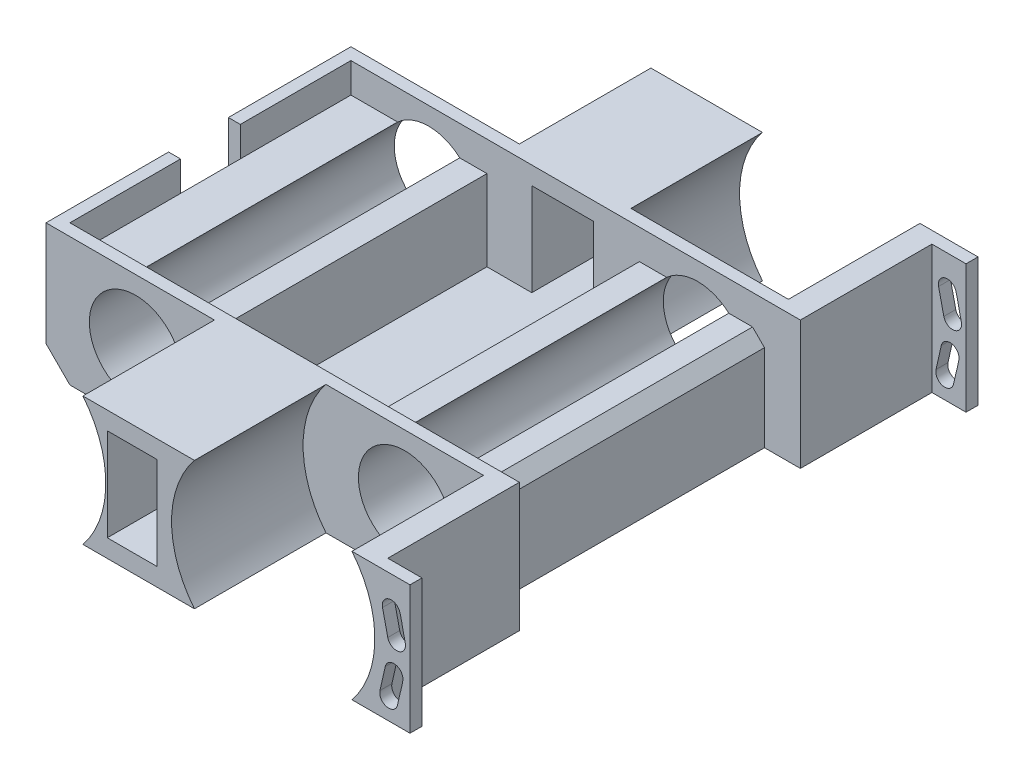
SolidWorks part; units mm, degrees
ref_plane "Front Plane" through (0, 0, 0) normal (0, 0, 1) x (1, 0, 0)
ref_plane "Top Plane" through (0, 0, 0) normal (0, 1, 0) x (1, 0, 0)
ref_plane "Right Plane" through (0, 0, 0) normal (1, 0, 0) x (0, 0, -1)
sketch "Sketch1" plane through (0, 0, 0) normal (0, 1, 0) x (1, 0, 0)
  line L1 (-44.2281, 29.9937) -> (50.7719, 29.9937)
  line L2 (-44.2281, 29.9937) -> (-44.2281, -65.0063)
  line L3 (-44.2281, -65.0063) -> (50.7719, -65.0063)
  line L4 (50.7719, 29.9937) -> (50.7719, -65.0063)
  dimension "D1" = 95
  dimension "D2" = 95
extrude "Boss-Extrude1" add sketch "Sketch1" along normal blind 25
sketch "Sketch2" plane through (0, 0, 65.0063) normal (0, 0, 1) x (1, 0, 0)
  line L1 (-44.2281, 0) -> (50.7719, 0) construction
  line L2 (-44.2281, 25) -> (-44.2281, 0) construction
  circle A0 centre (-29.2281, 10.75) radius 7.75
  circle A1 centre (15.7719, 10.75) radius 7.75
  point P6 (-44.2281, 12.5)
  dimension "D1" = 45
  dimension "D2" = 10.75
  dimension "D3" = 15
extrude "Cut-Extrude2" cut sketch "Sketch2" against normal blind 100
sketch "Sketch3" plane through (0, 0, 65.0063) normal (0, 0, 1) x (1, 0, 0)
  line L0 (-44.2281, 0) -> (50.7719, 0) construction
  circle A0 centre (-29.2281, 10.75) radius 17
  circle A1 centre (15.7719, 10.75) radius 17
  dimension "D1" = 45
  dimension "D2" = 10.75
extrude "Cut-Extrude3" cut sketch "Sketch3" against normal blind 22
sketch "Sketch4" plane through (0, 0, -29.9937) normal (0, 0, -1) x (-1, 0, 0)
  circle A0 centre (-15.7719, 10.75) radius 17
  circle A1 centre (29.2281, 10.75) radius 17
extrude "Cut-Extrude4" cut sketch "Sketch4" against normal blind 22
sketch "Sketch5" plane through (0, 0, 65.0063) normal (0, 0, 1) x (1, 0, 0)
  line L1 (-44.2281, 25) -> (-37.9811, 25)
  line L2 (-44.2281, 25) -> (-44.2281, 0)
  line L3 (-44.2281, 0) -> (-37.9811, 0)
  line L4 (-37.9811, 25) -> (-37.9811, 0)
extrude "Cut-Extrude5" cut sketch "Sketch5" against normal blind 22
sketch "Sketch6" plane through (0, 0, -29.9937) normal (0, 0, -1) x (-1, 0, 0)
  line L1 (44.2281, 25) -> (37.0493, 25)
  line L2 (44.2281, 25) -> (44.2281, 0)
  line L3 (44.2281, 0) -> (37.0493, 0)
  line L4 (37.0493, 25) -> (37.0493, 0)
extrude "Cut-Extrude6" cut sketch "Sketch6" against normal blind 22
sketch "Sketch8" plane through (0, 0, -29.9937) normal (0, 0, -1) x (-1, 0, 0)
  line L1 (-50.7719, 25) -> (48.732, 25)
  line L2 (-50.7719, 25) -> (-50.7719, 21.5)
  line L3 (-50.7719, 21.5) -> (48.732, 21.5)
  line L4 (48.732, 25) -> (48.732, 21.5)
  dimension "D1" = 3.5
extrude "Cut-Extrude7" cut sketch "Sketch8" against normal blind 100
sketch "Sketch9" plane through (0, 0, 65.0063) normal (0, 0, 1) x (1, 0, 0)
  line L0 (-16.0585, 0) -> (2.6024, 0) construction
  line L1 (-11.9781, 18.5) -> (-3.6781, 18.5)
  line L2 (-11.9781, 18.5) -> (-11.9781, 3)
  line L3 (-11.9781, 3) -> (-3.6781, 3)
  line L4 (-3.6781, 18.5) -> (-3.6781, 3)
  arc A0 (-16.0585, 0) -> (-16.0585, 21.5) centre (-29.2281, 10.75) ccw construction
  circle A1 centre (15.7719, 10.75) radius 7.75 construction
  dimension "D1" = 8.3
  dimension "D2" = 15.5
  dimension "D3" = 3
  dimension "D4" = 17.25
  dimension "D5" = 19.45
extrude "Cut-Extrude11" cut sketch "Sketch9" against normal blind 100
sketch "Sketch13" plane through (-3.6781, 0, 0) normal (-1, 0, 0) x (0, 0, 1)
  line L0 (-29.9937, 3) -> (65.0063, 3) construction
  line L1 (-25.9937, 3) -> (61.0063, 3)
  line L2 (-25.9937, 3) -> (-25.9937, 18.5)
  line L3 (-25.9937, 18.5) -> (61.0063, 18.5)
  line L4 (61.0063, 3) -> (61.0063, 18.5)
  line L5 (-29.9937, 18.5) -> (65.0063, 18.5) construction
  line L6 (-29.9937, 3) -> (-29.9937, 18.5) construction
  line L7 (65.0063, 3) -> (65.0063, 18.5) construction
  dimension "D1" = 4
  dimension "D2" = 4
extrude "Cut-Extrude12" cut sketch "Sketch13" against normal blind 2
sketch "Sketch14" plane through (0, 21.5, 0) normal (0, 1, 0) x (1, 0, 0)
  line L2 (6.0219, 5.9937) -> (6.0219, -41.0063)
  line L4 (-19.4781, 5.9937) -> (-19.4781, -41.0063)
  line L7 (6.0219, 5.9937) -> (-19.4781, 5.9937)
  line L9 (6.0219, -41.0063) -> (-19.4781, -41.0063)
  dimension "D2" = 2
extrude "Cut-Extrude14" cut sketch "Sketch14" against normal blind 18.5
sketch "Sketch16" plane through (0, 21.5, 0) normal (0, 1, 0) x (1, 0, 0)
  line L0 (-44.2281, -43.0063) -> (-44.2281, 7.9937) construction
  line L1 (-17.4781, 5.9937) -> (-42.2281, 5.9937)
  line L2 (-17.4781, 5.9937) -> (-17.4781, -41.0063)
  line L3 (-17.4781, -41.0063) -> (-42.2281, -41.0063)
  line L4 (-42.2281, 5.9937) -> (-42.2281, -41.0063)
  line L5 (-44.2281, -43.0063) -> (-16.0585, -43.0063) construction
  line L6 (-16.0585, 7.9937) -> (-44.2281, 7.9937) construction
  dimension "D1" = 2
  dimension "D2" = 2
  dimension "D3" = 2
  dimension "D4" = 2
extrude "Cut-Extrude15" cut sketch "Sketch16" against normal blind 5
sketch "Sketch17" plane through (0, 21.5, 0) normal (0, 1, 0) x (1, 0, 0)
  line L0 (2.6024, -43.0063) -> (28.9415, -43.0063) construction
  line L1 (6.0219, 5.9937) -> (26.9415, 5.9937)
  line L2 (6.0219, 5.9937) -> (6.0219, -41.0063)
  line L3 (6.0219, -41.0063) -> (26.9415, -41.0063)
  line L4 (26.9415, 5.9937) -> (26.9415, -41.0063)
  dimension "D1" = 2
  dimension "D2" = 2
extrude "Cut-Extrude16" cut sketch "Sketch17" against normal blind 5
sketch "Sketch18" plane through (0, 0, 65.0063) normal (0, 0, 1) x (1, 0, 0)
  line L0 (34.6664, 12.75) -> (37.6809, 12.75)
  line L2 (34.6664, 8.75) -> (37.6809, 8.75)
  line L3 (33.4355, 17.75) -> (36.6286, 17.75)
  line L4 (33.4355, 3.75) -> (36.6286, 3.75)
  arc A0 (36.6286, 3.75) -> (37.6809, 8.75) centre (15.7719, 10.75) ccw
  arc A1 (33.4355, 3.75) -> (34.6664, 8.75) centre (15.7719, 10.75) ccw
  arc A2 (34.6664, 12.75) -> (33.4355, 17.75) centre (15.7719, 10.75) ccw
  arc A3 (37.6809, 12.75) -> (36.6286, 17.75) centre (15.7719, 10.75) ccw
  dimension "D1" = 44
  dimension "D2" = 38
  dimension "D4" = 5
  dimension "D6" = 5
extrude "Cut-Extrude17" cut sketch "Sketch18" against normal blind 100
fillet "Fillet6" radius 1.5 2 edges at (33.4355, 17.75, 17.5063) (36.6286, 17.75, 17.5063)
fillet "Fillet7" radius 1.5 2 edges at (37.6809, 12.75, 17.5063) (34.6664, 12.75, 17.5063)
fillet "Fillet8" radius 1.5 2 edges at (33.4355, 3.75, 17.5063) (36.6286, 3.75, 17.5063)
fillet "Fillet9" radius 1.5 2 edges at (37.6809, 8.75, 17.5063) (34.6664, 8.75, 17.5063)
sketch "Sketch19" plane through (0, 0, 65.0063) normal (0, 0, 1) x (1, 0, 0)
  line L1 (28.9415, 0) -> (50.7719, 0) construction
  line L2 (38.6507, 0) -> (50.7719, 0)
  line L3 (38.6507, 0) -> (38.6507, 21.5)
  line L4 (38.6507, 21.5) -> (50.7719, 21.5)
  line L5 (50.7719, 0) -> (50.7719, 21.5)
extrude "Cut-Extrude20" cut sketch "Sketch19" against normal blind 100
sketch "Sketch20" plane through (0, 21.5, 0) normal (0, 1, 0) x (1, 0, 0)
  line L0 (38.6507, -65.0063) -> (38.6507, 29.9937) construction
  line L1 (38.6507, -63.0063) -> (32.9415, -63.0063)
  line L2 (38.6507, -63.0063) -> (38.6507, 27.9937)
  line L3 (38.6507, 27.9937) -> (32.9415, 27.9937)
  line L4 (32.9415, -63.0063) -> (32.9415, 27.9937)
  line L5 (38.6507, 29.9937) -> (28.9415, 29.9937) construction
  line L6 (38.6507, -65.0063) -> (28.9415, -65.0063) construction
  line L7 (28.9415, -65.0063) -> (28.9415, -43.0063) construction
  dimension "D1" = 2
  dimension "D2" = 2
  dimension "D3" = 4
extrude "Cut-Extrude23" cut sketch "Sketch20" against normal blind 100
sketch "Sketch21" plane through (0, 21.5, 0) normal (0, 1, 0) x (1, 0, 0)
  line L0 (32.9415, 27.9937) -> (32.9415, -63.0063) construction
  line L1 (26.9415, -41.0063) -> (32.9415, -41.0063)
  line L2 (26.9415, -41.0063) -> (26.9415, 5.9937)
  line L3 (26.9415, 5.9937) -> (32.9415, 5.9937)
  line L4 (32.9415, -41.0063) -> (32.9415, 5.9937)
  line L6 (28.9415, 7.9937) -> (2.6024, 7.9937) construction
  dimension "D1" = 2
extrude "Cut-Extrude26" cut sketch "Sketch21" against normal blind 40
chamfer "Chamfer1" distance 2 angle 45 1 edges at (26.9415, 16.5, 17.5063)
sketch "Sketch22" plane through (0, 0, 0) normal (0, -1, 0) x (-1, 0, 0)
  line L0 (44.2281, 7.9937) -> (44.2281, -43.0063) construction
  line L1 (42.2281, -12.5063) -> (27.2281, -12.5063)
  line L2 (42.2281, -12.5063) -> (42.2281, -22.5063)
  line L3 (42.2281, -22.5063) -> (27.2281, -22.5063)
  line L4 (27.2281, -12.5063) -> (27.2281, -22.5063)
  line L5 (16.0585, 7.9937) -> (44.2281, 7.9937) construction
  line L6 (44.2281, -43.0063) -> (16.0585, -43.0063) construction
  dimension "D1" = 10
  dimension "D2" = 15
  dimension "D3" = 2
  dimension "D4" = 20.5
  dimension "D5" = 20.5
extrude "Cut-Extrude27" cut sketch "Sketch22" against normal blind 4
sketch "Sketch23" plane through (0, 0, 0) normal (0, -1, 0) x (-1, 0, 0)
  line L0 (44.2281, 7.9937) -> (44.2281, -43.0063) construction
  line L1 (42.2281, -12.5063) -> (44.2281, -12.5063)
  line L2 (42.2281, -12.5063) -> (42.2281, -22.5063)
  line L3 (42.2281, -22.5063) -> (44.2281, -22.5063)
  line L4 (44.2281, -12.5063) -> (44.2281, -22.5063)
  dimension "D1" = 10
extrude "Cut-Extrude28" cut sketch "Sketch23" against normal blind 54
chamfer "Chamfer2" distance 2 angle 45 1 edges at (-42.2281, 4, 17.5063)
chamfer "Chamfer3" distance 4 angle 45 1 edges at (-44.2281, 0, 2.2563)
chamfer "Chamfer4" distance 4 angle 45 1 edges at (-44.2281, 0, 32.7563)
sketch "Sketch24" plane through (0, 0, 65.0063) normal (0, 0, 1) x (1, 0, 0)
  line L0 (35.5204, 16.25) -> (36.3995, 12.3478) construction
  line L1 (36.9837, 16.5797) -> (37.8628, 12.6775)
  line L2 (34.057, 15.9203) -> (34.9362, 12.0181)
  line L3 (35.971, 7.25) -> (35.0918, 3.3478) construction
  line L4 (37.4343, 6.9203) -> (36.5551, 3.0181)
  line L5 (34.5076, 7.5797) -> (33.6285, 3.6775)
  arc A5 (36.9837, 16.5797) -> (34.057, 15.9203) centre (35.5204, 16.25) ccw
  arc A6 (34.9362, 12.0181) -> (37.8628, 12.6775) centre (36.3995, 12.3478) ccw
  arc A7 (37.4343, 6.9203) -> (34.5076, 7.5797) centre (35.971, 7.25) ccw
  arc A8 (33.6285, 3.6775) -> (36.5551, 3.0181) centre (35.0918, 3.3478) ccw
  point P3 (35.9599, 14.2989)
  point P10 (35.5314, 5.2989)
extrude "Cut-Extrude29" cut sketch "Sketch24" against normal blind 100
